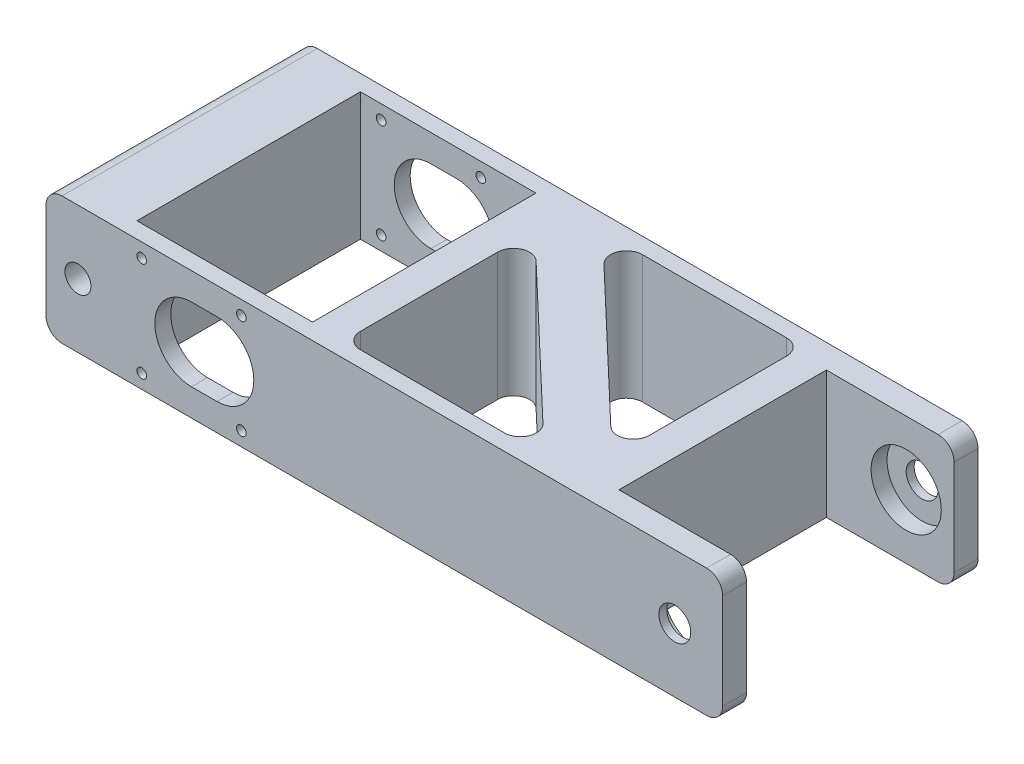
SolidWorks part; units mm, degrees
ref_plane "Front Plane" through (0, 0, 0) normal (0, 0, 1) x (1, 0, 0)
ref_plane "Top Plane" through (0, 0, 0) normal (0, 1, 0) x (1, 0, 0)
ref_plane "Right Plane" through (0, 0, 0) normal (1, 0, 0) x (0, 0, -1)
sketch "Sketch1" plane through (0, 0, 0) normal (0, 0, 1) x (1, 0, 0)
  line L0 (-106, -20) -> (-106, 20)
  line L1 (-106, 20) -> (106, 20)
  line L3 (-106, -20) -> (106, -20)
  line L4 (106, 20) -> (106, -20)
  line L5 (-106, 20) -> (106, -20) construction
  line L6 (-106, -20) -> (106, 20) construction
  line L7 (-76, 15.6) -> (-76, -15.6) construction
  line L9 (-76, 15.6) -> (-68, 15.6) construction
  line L10 (-76, 17.1) -> (-68, 17.1) construction
  line L11 (-76, 14.1) -> (-68, 14.1) construction
  line L12 (-44.8, 15.6) -> (-36.8, 15.6) construction
  line L13 (-44.8, 17.1) -> (-36.8, 17.1) construction
  line L14 (-44.8, 14.1) -> (-36.8, 14.1) construction
  line L15 (-76, -15.6) -> (-68, -15.6) construction
  line L16 (-76, -14.1) -> (-68, -14.1) construction
  line L17 (-76, -17.1) -> (-68, -17.1) construction
  line L18 (-44.8, -15.6) -> (-36.8, -15.6) construction
  line L19 (-44.8, -14.1) -> (-36.8, -14.1) construction
  line L20 (-44.8, -17.1) -> (-36.8, -17.1) construction
  line L21 (-60.4, 0) -> (-52.4, 0) construction
  line L22 (-60.4, 11.5) -> (-52.4, 11.5)
  line L23 (-60.4, -11.5) -> (-52.4, -11.5)
  circle A0 centre (-96, 0) radius 4.075
  circle A1 centre (-76, 15.6) radius 1.5
  circle A2 centre (-44.8, 15.6) radius 1.5
  circle A3 centre (-76, -15.6) radius 1.5
  circle A4 centre (-44.8, -15.6) radius 1.5
  circle A5 centre (-60.4, 0) radius 11.5 construction
  circle A6 centre (91, 0) radius 5
  arc A7 (-76, 17.1) -> (-76, 14.1) centre (-76, 15.6) ccw construction
  arc A8 (-68, 14.1) -> (-68, 17.1) centre (-68, 15.6) ccw construction
  arc A9 (-44.8, 17.1) -> (-44.8, 14.1) centre (-44.8, 15.6) ccw construction
  arc A10 (-36.8, 14.1) -> (-36.8, 17.1) centre (-36.8, 15.6) ccw construction
  arc A11 (-76, -14.1) -> (-76, -17.1) centre (-76, -15.6) ccw construction
  arc A12 (-68, -17.1) -> (-68, -14.1) centre (-68, -15.6) ccw construction
  arc A13 (-44.8, -14.1) -> (-44.8, -17.1) centre (-44.8, -15.6) ccw construction
  arc A14 (-36.8, -17.1) -> (-36.8, -14.1) centre (-36.8, -15.6) ccw construction
  arc A15 (-60.4, 11.5) -> (-60.4, -11.5) centre (-60.4, 0) ccw
  arc A16 (-52.4, -11.5) -> (-52.4, 11.5) centre (-52.4, 0) ccw
  point P0 (0, 0)
  point P16 (-76, 0)
  point P22 (-72, 15.6)
  point P28 (-40.8, 15.6)
  point P34 (-72, -15.6)
  point P40 (-40.8, -15.6)
  point P47 (-56.4, 0)
  point P54 (0, 0)
  point P55 (0, 0)
  point P56 (0, 0)
  dimension "D3" = 8.15
  dimension "D5" = 31.2
  dimension "D1" = 3
  dimension "D7" = 31.2
  dimension "D9" = 23
  dimension "D10" = 10
  dimension "D4" = 10
  dimension "D2" = 212
  dimension "D6" = 40
  dimension "D8" = 20
  dimension "D11" = 15
  dimension "D12" = 4
  dimension "D13" = 15.6
extrude "Boss-Extrude1" add sketch "Sketch1" along normal mid plane 80 contours L4 L1 L0 L3 A14 L20 A13 L19 A12 L17 A11 L16 A10 L14 A9 A8 L11 A7 L10 L13 A6 A5 A0 region at (4.3229, 0, 0)
sketch "Sketch2" plane through (0, 0, 0) normal (0, 1, 0) x (1, 0, 0)
  line L0 (-106, 40) -> (106, 40) construction
  line L1 (-82.5, 35) -> (-27.5, 35)
  line L2 (-82.5, 35) -> (-82.5, -35)
  line L3 (-82.5, -35) -> (-27.5, -35)
  line L4 (-27.5, 35) -> (-27.5, -35)
  line L5 (-82.5, 35) -> (-27.5, -35) construction
  line L6 (-82.5, -35) -> (-27.5, 35) construction
  line L7 (-17.5, 24.6429) -> (45.125, -35)
  line L8 (106, -40) -> (106, 40) construction
  line L9 (66, 32.5) -> (106, 32.5)
  line L10 (66, 32.5) -> (66, -32.5)
  line L11 (66, -32.5) -> (106, -32.5)
  line L12 (106, 32.5) -> (106, -32.5)
  line L13 (66, 32.5) -> (106, -32.5) construction
  line L14 (66, -32.5) -> (106, 32.5) construction
  line L15 (-17.5, 35) -> (56, 35) construction
  line L16 (-17.5, 35) -> (-17.5, -35) construction
  line L17 (-17.5, -35) -> (56, -35) construction
  line L18 (56, 35) -> (56, -35) construction
  line L19 (-17.5, 35) -> (56, -35) construction
  line L20 (-17.5, -35) -> (56, 35) construction
  line L21 (-6.625, 35) -> (56, -24.6429)
  line L22 (-17.5, 24.6429) -> (-17.5, -35)
  line L23 (-6.625, 35) -> (56, 35)
  line L24 (56, 35) -> (56, -24.6429)
  line L25 (-17.5, -35) -> (45.125, -35)
  line L26 (-106, -40) -> (106, -40) construction
  point P0 (-55, 0)
  point P10 (19.25, 0)
  point P11 (86, 0)
  dimension "D1" = 55
  dimension "D2" = 5
  dimension "D3" = 55
  dimension "D4" = 40
  dimension "D5" = 10
  dimension "D6" = 10
  dimension "D7" = 15
  dimension "D8" = 7.5
extrude "Cut-Extrude3" cut sketch "Sketch2" against normal through all both and the other way through all
fillet "Fillet1" radius 5 6 edges at (45.125, 0, 35) (-17.5, 0, 35) (56, 0, 24.6429) (56, 0, -35) (-6.625, 0, -35) (-17.5, 0, -24.6429)
fillet "Fillet2" radius 5 6 edges at (-106, 20, 0) (-106, -20, 0) (106, 20, 36.25) (106, -20, 36.25) (106, 20, -36.25) (106, -20, -36.25)
sketch "Sketch4" plane through (0, 0, 0) normal (0, 0, 1) x (1, 0, 0)
  circle A0 centre (91, 0) radius 11
  dimension "D1" = 22
extrude "Cut-Extrude4" cut sketch "Sketch4" against normal mid plane 75
